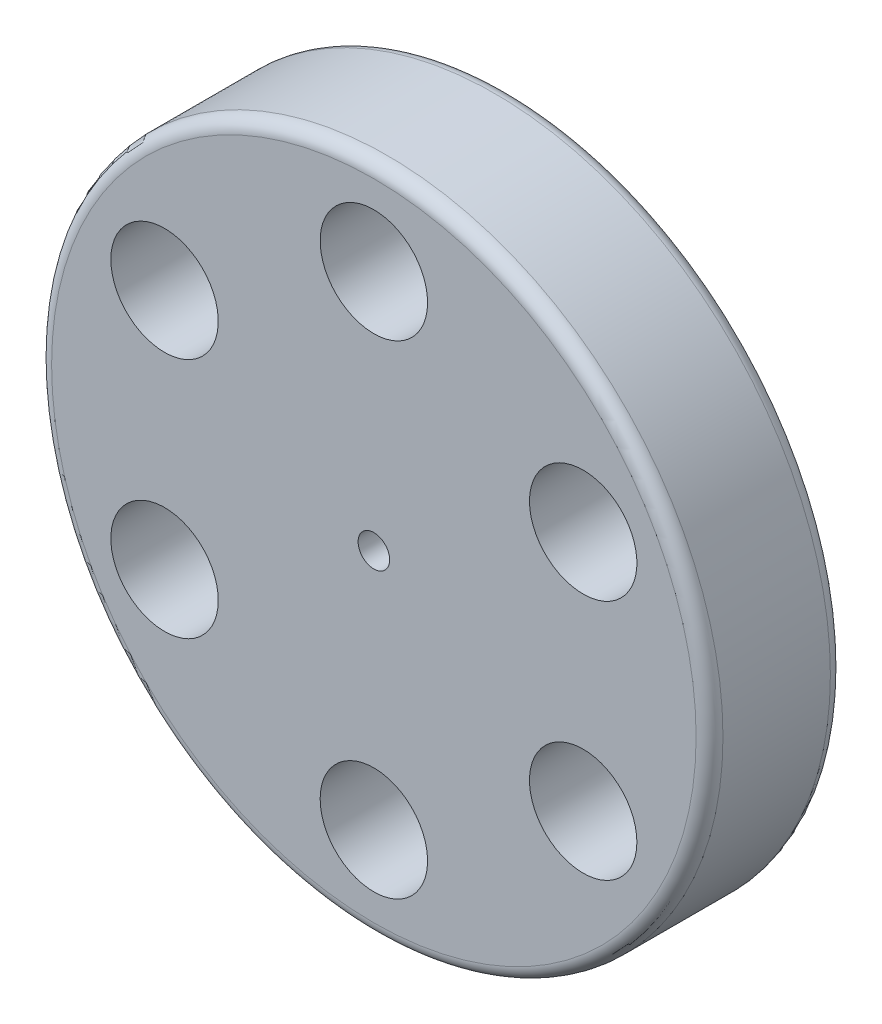
SolidWorks part; units mm, degrees
material "ABS"
ref_plane "Front" through (0, 0, 0) normal (0, 0, 1) x (1, 0, 0)
ref_plane "Top" through (0, 0, 0) normal (0, 1, 0) x (1, 0, 0)
ref_plane "Right" through (0, 0, 0) normal (1, 0, 0) x (0, 0, -1)
sketch "Sketch1" plane through (0, 0, 0) normal (0, 0, 1) x (1, 0, 0)
  circle A0 centre (0, 0) radius 25
  dimension "D1" = 50
extrude "Boss-Extrude1" add sketch "Sketch1" along normal blind 10
sketch "Sketch2" plane through (0, 0, 10) normal (0, 0, 1) x (1, 0, 0)
  circle A0 centre (0, 0) radius 1.175
  dimension "D1" = 2.35
extrude "Cut-Extrude2" cut sketch "Sketch2" against normal blind 9
sketch "Sketch3" plane through (0, 0, 10) normal (0, 0, 1) x (1, 0, 0)
  circle A0 centre (0, 18) radius 4
  dimension "D1" = 8
  dimension "D2" = 18
extrude "Cut-Extrude3" cut sketch "Sketch3" against normal through all
pattern_circular "CirPattern1" count 6 over 360 about axis through (0, 0, 10) along (0, 0, 1) of "Cut-Extrude3"
fillet "Fillet1" radius 1 2 edges at (25, 0, 0) (25, 0, 10)
